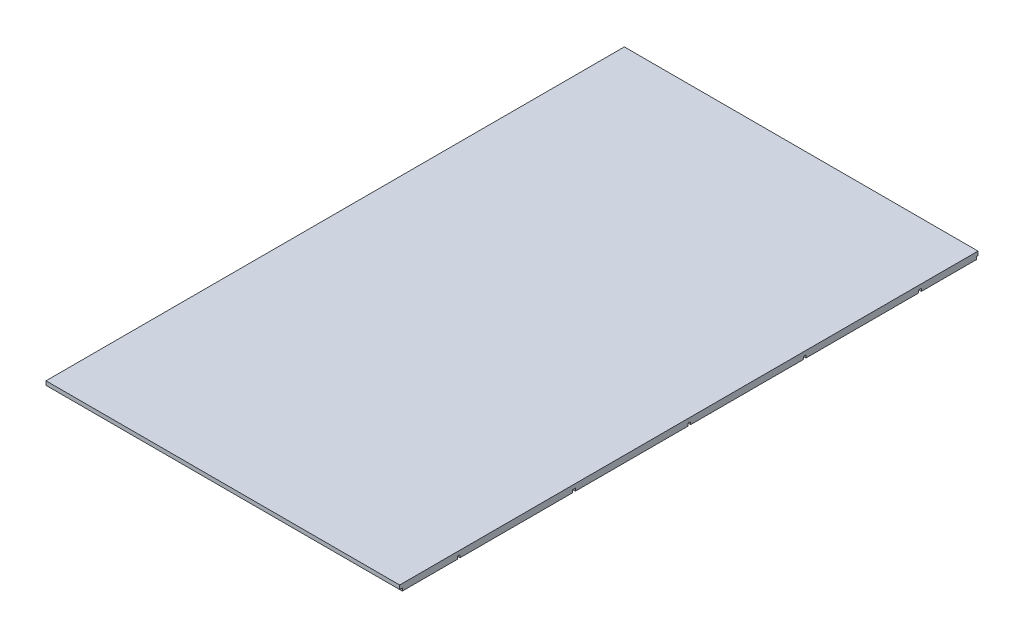
SolidWorks part; units mm, degrees
ref_plane "Front Plane" through (0, 0, 0) normal (0, 0, 1) x (1, 0, 0)
ref_plane "Top Plane" through (0, 0, 0) normal (0, 1, 0) x (1, 0, 0)
ref_plane "Right Plane" through (0, 0, 0) normal (1, 0, 0) x (0, 0, -1)
sketch "Sketch1" plane through (0, 0, 0) normal (0, 1, 0) x (1, 0, 0)
  line L1 (-35.052, 70.358) -> (35.052, 70.358)
  line L2 (-35.052, 70.358) -> (-35.052, -70.358)
  line L3 (-35.052, -70.358) -> (35.052, -70.358)
  line L4 (35.052, 70.358) -> (35.052, -70.358)
  line L5 (-35.052, 70.358) -> (35.052, -70.358) construction
  line L6 (-35.052, -70.358) -> (35.052, 70.358) construction
  point P0 (0, 0)
  dimension "D1" = 70.104
  dimension "D2" = 140.716
extrude "Boss-Extrude1" add sketch "Sketch1" along normal blind 1.27
sketch "Sketch2" plane through (0, 1.27, 0) normal (0, 1, 0) x (1, 0, 0)
  line L0 (-35.052, -70.358) -> (0, -70.358)
  line L1 (-35.052, -70.358) -> (35.052, -70.358) construction
  line L2 (-35.052, 70.358) -> (-35.052, -70.358)
  line L3 (-35.052, 70.358) -> (35.052, 70.358)
  line L4 (-33.782, 69.088) -> (-33.782, -69.088)
  line L5 (0, -70.358) -> (35.052, -70.358)
  line L6 (-33.782, -69.088) -> (33.782, -69.088)
  line L7 (35.052, 70.358) -> (35.052, -70.358)
  line L9 (33.782, 69.088) -> (33.782, -69.088)
  line L12 (-33.782, 69.088) -> (33.782, 69.088)
  dimension "D1" = 1.27
  dimension "D2" = 1.27
  dimension "D3" = 1.27
  dimension "D5" = 1.27
extrude "Boss-Extrude2" add sketch "Sketch2" along normal blind 8.382
sketch "Sketch3" plane through (-35.052, 0, 0) normal (-1, 0, 0) x (0, 0, 1)
  line L0 (-70.358, 9.652) -> (70.358, 9.652) construction
  line L1 (-55.118, 9.652) -> (-13.208, 9.652)
  line L2 (-55.118, 9.652) -> (-55.118, 1.27)
  line L3 (-55.118, 1.27) -> (-13.208, 1.27)
  line L4 (-13.208, 9.652) -> (-13.208, 1.27)
  line L5 (-70.358, 9.652) -> (-70.358, 0) construction
  line L6 (-70.358, 0) -> (70.358, 0) construction
  dimension "D1" = 15.24
  dimension "D2" = 57.15
  dimension "D3" = 1.27
extrude "Cut-Extrude1" cut sketch "Sketch3" against normal blind 1.27
sketch "Sketch5" plane through (35.052, 0, 0) normal (1, 0, 0) x (0, 0, -1)
  line L0 (-70.358, 9.652) -> (70.358, 9.652) construction
  line L1 (24.638, 9.652) -> (43.688, 9.652)
  line L2 (24.638, 9.652) -> (24.638, 1.27)
  line L3 (24.638, 1.27) -> (43.688, 1.27)
  line L4 (43.688, 9.652) -> (43.688, 1.27)
  line L5 (70.358, 9.652) -> (70.358, 0) construction
  line L6 (-70.358, 0) -> (70.358, 0) construction
  dimension "D1" = 26.67
  dimension "D2" = 45.72
  dimension "D3" = 1.27
extrude "Cut-Extrude2" cut sketch "Sketch5" against normal blind 1.27
sketch "Sketch6" plane through (0, 0, 70.358) normal (0, 0, 1) x (1, 0, 0)
  line L1 (-35.052, 9.652) -> (35.052, 9.652) construction
  line L2 (-27.432, 9.652) -> (27.432, 9.652)
  line L3 (-27.432, 9.652) -> (-27.432, 1.27)
  line L4 (-27.432, 1.27) -> (27.432, 1.27)
  line L8 (27.432, 9.652) -> (27.432, 1.27)
  line L9 (-35.052, 9.652) -> (-35.052, 0) construction
  line L10 (35.052, 9.652) -> (35.052, 0) construction
  line L11 (-35.052, 0) -> (35.052, 0) construction
  dimension "D1" = 7.62
  dimension "D2" = 7.62
  dimension "D3" = 1.27
extrude "Cut-Extrude3" cut sketch "Sketch6" against normal blind 1.27
sketch "Sketch7" plane through (0, 0, 0) normal (0, -1, 0) x (1, 0, 0)
  line L0 (35.052, 70.358) -> (35.052, -70.358) construction
  line L1 (26.162, -57.658) -> (4.572, -57.658)
  line L2 (26.162, -57.658) -> (26.162, -66.548)
  line L3 (26.162, -66.548) -> (4.572, -66.548)
  line L4 (4.572, -57.658) -> (4.572, -66.548)
  line L5 (35.052, -70.358) -> (-35.052, -70.358) construction
  dimension "D1" = 8.89
  dimension "D2" = 30.48
  dimension "D3" = 3.81
  dimension "D4" = 12.7
extrude "Cut-Extrude4" cut sketch "Sketch7" against normal blind 1.27
fillet "Fillet1" radius 10.16 4 edges at (33.782, 5.461, -69.088) (-33.782, 5.461, -69.088) (-33.782, 5.461, 69.088) (33.782, 5.461, 69.088)
fillet "Fillet2" radius 10.16 4 edges at (-35.052, 4.826, -70.358) (35.052, 4.826, -70.358) (35.052, 4.826, 70.358) (-35.052, 4.826, 70.358)
sketch "Sketch8" plane through (-33.782, 0, 0) normal (1, 0, 0) x (0, 0, -1)
  line L0 (58.928, 1.27) -> (58.928, 9.652) construction
  line L1 (55.118, 9.652) -> (58.928, 9.652)
  line L2 (55.118, 9.652) -> (55.118, 8.382)
  line L3 (55.118, 8.382) -> (58.928, 8.382)
  line L4 (58.928, 9.652) -> (58.928, 8.382)
  dimension "D1" = 1.27
extrude "Boss-Extrude3" add sketch "Sketch8" along normal blind 1.27
sketch "Sketch13" plane through (0, 0, -69.088) normal (0, 0, 1) x (1, 0, 0)
  line L0 (23.622, 1.27) -> (23.622, 9.652) construction
  line L1 (-23.622, 9.652) -> (23.622, 9.652)
  line L2 (-23.622, 9.652) -> (-23.622, 8.382)
  line L3 (-23.622, 8.382) -> (23.622, 8.382)
  line L4 (23.622, 9.652) -> (23.622, 8.382)
  dimension "D1" = 1.27
extrude "Boss-Extrude6" [suppressed] add sketch "Sketch13" along normal blind 1.27
sketch "Sketch14" plane through (33.782, 0, 0) normal (-1, 0, 0) x (0, 0, 1)
  line L0 (-43.688, 1.27) -> (-43.688, 9.652) construction
  line L1 (-58.928, 9.652) -> (-43.688, 9.652)
  line L2 (-58.928, 9.652) -> (-58.928, 8.382)
  line L3 (-58.928, 8.382) -> (-43.688, 8.382)
  line L4 (-43.688, 9.652) -> (-43.688, 8.382)
  dimension "D1" = 1.27
extrude "Boss-Extrude7" add sketch "Sketch14" along normal blind 1.27
sketch "Sketch19" plane through (33.782, 0, 0) normal (-1, 0, 0) x (0, 0, 1)
  line L1 (59.6694, 1.27) -> (59.6694, 9.652) construction
  line L2 (-24.638, 9.652) -> (59.6694, 9.652)
  line L3 (-24.638, 9.652) -> (-24.638, 8.382)
  line L4 (-24.638, 8.382) -> (59.6694, 8.382)
  line L5 (59.6694, 9.652) -> (59.6694, 8.382)
  dimension "D1" = 1.27
extrude "Boss-Extrude8" add sketch "Sketch19" along normal blind 1.27
sketch "Sketch20" plane through (-33.782, 0, 0) normal (1, 0, 0) x (0, 0, -1)
  line L1 (-59.6694, 9.652) -> (-59.6694, 1.27) construction
  line L2 (13.208, 9.652) -> (-59.6694, 9.652)
  line L3 (13.208, 9.652) -> (13.208, 8.382)
  line L4 (13.208, 8.382) -> (-59.6694, 8.382)
  line L5 (-59.6694, 9.652) -> (-59.6694, 8.382)
  dimension "D1" = 1.27
extrude "Boss-Extrude9" add sketch "Sketch20" along normal blind 1.27
fillet "Fillet9" radius 3.81 4 edges at (26.162, 0.635, -57.658) (26.162, 0.635, -66.548) (4.572, 0.635, -66.548) (4.572, 0.635, -57.658)
fillet "Fillet12" radius 1.27 8 edges at (32.0762, 0, 67.3822) (0, 0, 70.358) (-32.0762, 0, 67.3822) (-35.052, 0, 0) (-32.0762, 0, -67.3822) (0, 0, -70.358) (32.0762, 0, -67.3822) (35.052, 0, 0)
fillet "Fillet15" radius 1.27 9 edges at (32.9242, 9.652, 66.4197) (-32.9242, 9.652, 66.4197) (35.052, 9.652, -51.943) (32.0762, 9.652, -67.3822) (-35.052, 9.652, -57.658) (35.052, 9.652, 17.78) (-35.052, 9.652, 23.495) (-32.0762, 9.652, -67.3822) (0, 9.652, -70.358)
fillet "Fillet16" radius 2.54 9 edges at (33.782, 1.27, -51.308) (30.8062, 1.27, -66.1122) (-33.782, 1.27, -57.023) (-30.8062, 1.27, -66.1122) (33.782, 1.27, 17.5157) (-33.782, 1.27, 23.2307) (0, 1.27, -69.088) (32.0462, 1.27, 65.349) (-32.0462, 1.27, 65.349)
sketch "Sketch28" plane through (0, 1.27, 0) normal (0, 1, 0) x (1, 0, 0)
  line L0 (31.242, 24.638) -> (35.052, 24.638) construction
  line L1 (35.052, 43.688) -> (33.782, 43.688)
  line L2 (35.052, 43.688) -> (35.052, 24.638)
  line L3 (35.052, 24.638) -> (33.782, 24.638)
  line L4 (33.782, 43.688) -> (33.782, 24.638)
  line L5 (-31.242, 13.208) -> (-35.052, 13.208) construction
  line L6 (-35.052, 55.118) -> (-33.782, 55.118)
  line L7 (-35.052, 55.118) -> (-35.052, 13.208)
  line L8 (-35.052, 13.208) -> (-33.782, 13.208)
  line L9 (-33.782, 55.118) -> (-33.782, 13.208)
  dimension "D1" = 1.27
  dimension "D2" = 1.27
extrude "Cut-Extrude10" cut sketch "Sketch28" against normal blind 1.27
fillet "Fillet18" radius 1.27 4 edges at (33.782, 8.382, -51.308) (-33.782, 8.382, -57.023) (33.782, 8.382, 17.5157) (-33.782, 8.382, 23.2307)
sketch "스케치1" plane through (0, 0, 0) normal (0, -1, 0) x (-1, 0, 0)
  line L0 (33.782, 55.118) -> (-33.782, 55.118)
  line L1 (-33.782, 60.198) -> (-33.782, 43.688) construction
  line L3 (33.782, -55.118) -> (-33.782, -55.118)
  line L4 (33.782, -60.198) -> (33.782, 13.208) construction
  line L5 (-33.782, 24.638) -> (-33.782, -60.198) construction
  line L6 (-24.892, -69.088) -> (24.892, -69.088) construction
  line L7 (33.782, -44.0944) -> (-33.782, -44.0944)
  line L8 (33.782, 44.0436) -> (-33.782, 44.0436)
  line L11 (33.782, -22.0599) -> (-33.782, -22.0599)
  line L12 (33.782, -0.0254) -> (-33.782, -0.0254)
  line L13 (33.782, 22.0091) -> (-33.782, 22.0091)
  line L15 (33.782, 13.208) -> (33.782, 55.118) construction
  line L16 (-33.782, 43.688) -> (-33.782, 24.638) construction
  line L17 (24.892, 69.088) -> (-24.892, 69.088) construction
  line L18 (0, -55.118) -> (33.782, -22.0599)
  line L19 (0, 55.118) -> (33.782, 22.0091)
  dimension "D1" = 22.0345
  dimension "D2" = 13.97
  dimension "D3" = 13.97
  dimension "D4" = 11.0236
  dimension "D7" = 22.0345
  dimension "D8" = 22.0345
  dimension "D9" = 22.0345
extrude "컷-돌출-얇게1" cut sketch "스케치1" against normal blind 0.508 thin thin type two direction wall 0.254 second wall 0.254
sketch "스케치3" plane through (0, 0, 0) normal (0, -1, 0) x (1, 0, 0)
  line L1 (-35.052, 55.372) -> (35.052, 55.372)
  line L2 (-35.052, 55.372) -> (-35.052, 70.358)
  line L3 (-35.052, 70.358) -> (35.052, 70.358)
  line L4 (35.052, 55.372) -> (35.052, 70.358)
  line L5 (-35.052, 55.372) -> (35.052, 70.358) construction
  line L6 (-35.052, 70.358) -> (35.052, 55.372) construction
  line L7 (-33.782, 55.372) -> (33.782, 55.372) construction
  line L8 (-24.892, 70.358) -> (24.892, 70.358) construction
  line L9 (-35.052, -13.208) -> (-35.052, 60.198) construction
  line L12 (35.052, 60.198) -> (35.052, -24.638) construction
  point P0 (0, 62.865)
extrude "컷-돌출1" cut sketch "스케치3" against normal blind 15.748
sketch "스케치4" plane through (0, 0, 0) normal (0, -1, 0) x (1, 0, 0)
  line L1 (-35.052, -55.118) -> (35.052, -55.118)
  line L2 (-35.052, -55.118) -> (-35.052, -70.358)
  line L3 (-35.052, -70.358) -> (35.052, -70.358)
  line L4 (35.052, -55.118) -> (35.052, -70.358)
  line L5 (-35.052, -55.118) -> (35.052, -70.358) construction
  line L6 (-35.052, -70.358) -> (35.052, -55.118) construction
  line L11 (-33.782, -55.118) -> (-35.052, -55.118) construction
  line L13 (-35.052, -60.198) -> (-35.052, -55.118) construction
  line L14 (35.052, -43.688) -> (35.052, -60.198) construction
  line L15 (24.892, -70.358) -> (-24.892, -70.358) construction
  point P0 (0, -62.738)
extrude "컷-돌출3" cut sketch "스케치4" against normal blind 15.748
sketch "스케치5" plane through (-35.052, 0, 0) normal (-1, 0, 0) x (0, 0, 1)
  line L0 (-13.208, 9.652) -> (55.372, 9.652) construction
  line L1 (-13.208, 1.27) -> (55.372, 1.27) construction
  line L2 (55.372, 8.382) -> (55.372, 1.27) construction
  line L3 (-55.118, 3.81) -> (-55.118, 7.112) construction
  line L4 (-55.118, 9.652) -> (55.372, 9.652)
  line L5 (-55.118, 9.652) -> (-55.118, 1.27)
  line L6 (-55.118, 1.27) -> (55.372, 1.27)
  line L7 (55.372, 9.652) -> (55.372, 1.27)
  line L8 (-55.118, 9.652) -> (55.372, 1.27) construction
  line L9 (-55.118, 1.27) -> (55.372, 9.652) construction
  point P3 (0.127, 5.461)
extrude "컷-돌출4" cut sketch "스케치5" against normal blind 85.09 and the other way blind 7.366
sketch "스케치6" plane through (0, 0, 0) normal (0, -1, 0) x (-1, 0, 0)
  line L0 (33.782, -54.864) -> (33.782, -44.3484) construction
  line L1 (35.052, -55.372) -> (33.782, -55.372)
  line L2 (35.052, -55.372) -> (35.052, 13.208)
  line L3 (35.052, 13.208) -> (33.782, 13.208)
  line L4 (33.782, -55.372) -> (33.782, 13.208)
  line L5 (35.052, -55.372) -> (33.782, 13.208) construction
  line L6 (35.052, 13.208) -> (33.782, -55.372) construction
  line L7 (35.052, 13.208) -> (35.052, -55.372) construction
  line L8 (35.052, 13.208) -> (33.782, 13.208) construction
  line L10 (33.782, -55.372) -> (35.052, -55.372) construction
  point P0 (34.417, -21.082)
extrude "컷-돌출7" cut sketch "스케치6" against normal blind 85.09
sketch "스케치7" plane through (0, 0, 0) normal (0, -1, 0) x (-1, 0, 0)
  line L0 (-33.782, -44.3484) -> (-33.782, -54.864) construction
  line L1 (-35.052, 55.118) -> (-33.782, 55.118)
  line L2 (-35.052, 55.118) -> (-35.052, -55.372)
  line L3 (-35.052, -55.372) -> (-33.782, -55.372)
  line L4 (-33.782, 55.118) -> (-33.782, -55.372)
  line L5 (-35.052, 55.118) -> (-33.782, -55.372) construction
  line L6 (-35.052, -55.372) -> (-33.782, 55.118) construction
  line L7 (-35.052, -55.372) -> (-33.782, -55.372) construction
  line L8 (-35.052, -55.372) -> (-35.052, 24.638) construction
  line L9 (-33.782, 55.118) -> (-35.052, 55.118) construction
  point P0 (-34.417, -0.127)
extrude "컷-돌출8" cut sketch "스케치7" against normal blind 85.09
